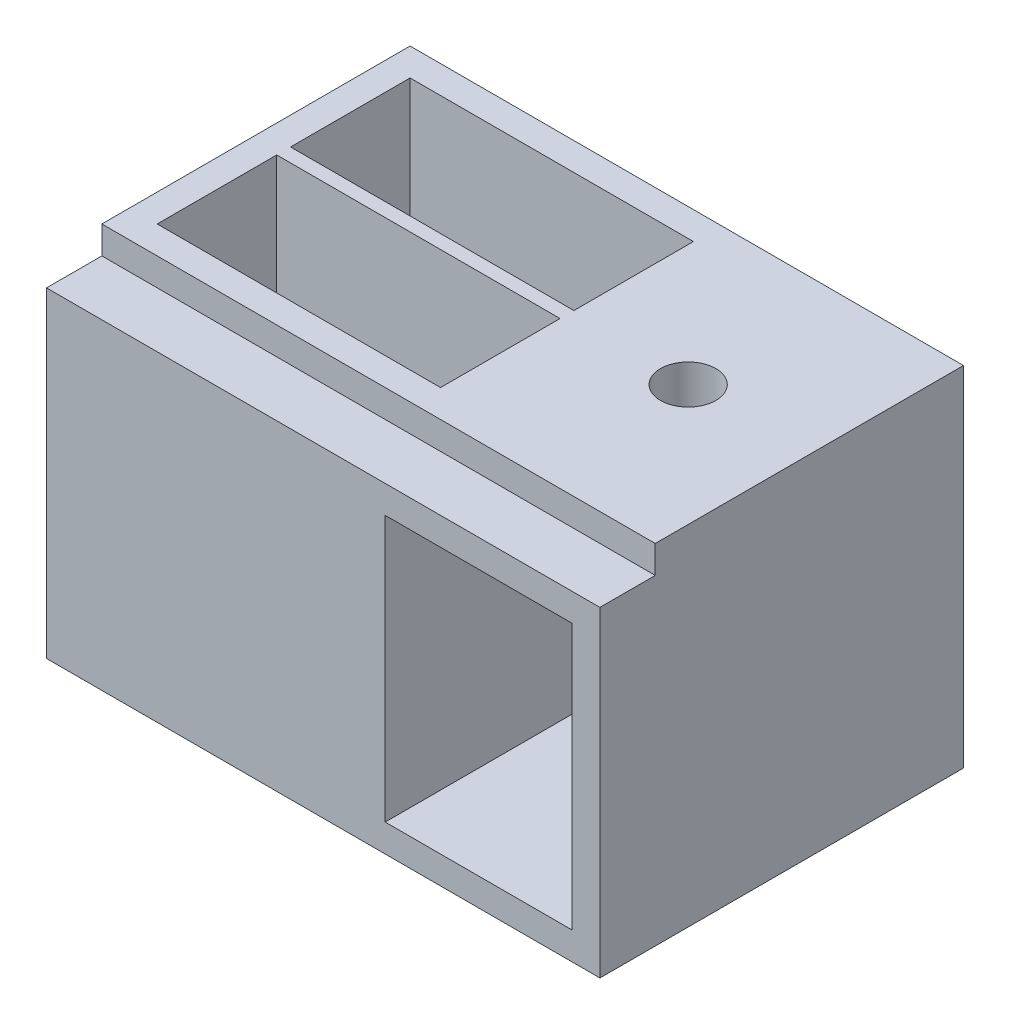
SolidWorks part; units mm, degrees
material "ABS"
ref_plane "Front Plane" through (0, 0, 0) normal (0, 0, 1) x (1, 0, 0)
ref_plane "Top Plane" through (0, 0, 0) normal (0, 1, 0) x (1, 0, 0)
ref_plane "Right Plane" through (0, 0, 0) normal (1, 0, 0) x (0, 0, -1)
sketch "Sketch1" plane through (0, 0, 0) normal (0, 1, 0) x (1, 0, 0)
  line L0 (3.175, 18.4785) -> (3.175, 32.1945)
  line L1 (0, 0) -> (63.5, 0)
  line L2 (0, 0) -> (0, 44.45)
  line L3 (0, 44.45) -> (63.5, 44.45)
  line L4 (63.5, 0) -> (63.5, 44.45)
  line L5 (4.445, 4.445) -> (34.417, 4.445)
  line L6 (4.445, 4.445) -> (4.445, 15.621)
  line L7 (4.445, 15.621) -> (34.417, 15.621)
  line L8 (34.417, 4.445) -> (34.417, 15.621)
  line L9 (4.445, 19.7485) -> (34.417, 19.7485)
  line L10 (4.445, 19.7485) -> (4.445, 30.9245)
  line L11 (4.445, 30.9245) -> (34.417, 30.9245)
  line L12 (34.417, 19.7485) -> (34.417, 30.9245)
  line L13 (3.175, 32.1945) -> (35.687, 32.1945)
  line L14 (35.687, 18.4785) -> (35.687, 32.1945)
  line L15 (3.175, 18.4785) -> (35.687, 18.4785)
  line L16 (3.175, 3.175) -> (35.687, 3.175)
  line L17 (35.687, 3.175) -> (35.687, 16.891)
  line L18 (3.175, 16.891) -> (35.687, 16.891)
  line L19 (3.175, 3.175) -> (3.175, 16.891)
  dimension "D1" = 44.45
  dimension "D2" = 63.5
  dimension "D3" = 11.176
  dimension "D4" = 29.972
  dimension "D5" = 11.176
  dimension "D6" = 29.972
  dimension "D9" = 1.5875
  dimension "D10" = 3.175
  dimension "D11" = 3.175
  dimension "D7" = 1.27
  dimension "D8" = 1.27
extrude "Boss-Extrude1" add sketch "Sketch1" along normal blind 40.005 contours L16 L19 L18 L17 L1 L4 L3 L2 L15 L0 L13 L14 region at (37.4406, 0, -24.3223)
sketch "Sketch2" plane through (0, 0, 0) normal (0, -1, 0) x (1, 0, 0)
  line L0 (3.175, -32.1945) -> (35.687, -32.1945) construction
  line L1 (3.175, -18.4785) -> (3.175, -32.1945) construction
  line L2 (3.175, -18.4785) -> (35.687, -18.4785) construction
  line L3 (35.687, -18.4785) -> (35.687, -32.1945) construction
  line L4 (0, 0) -> (0, -44.45)
  line L5 (0, -44.45) -> (63.5, -44.45)
  line L6 (63.5, -44.45) -> (63.5, 0)
  line L7 (63.5, 0) -> (0, 0)
  line L8 (0, 0) -> (0, -44.45)
  line L9 (0, -44.45) -> (63.5, -44.45)
  line L10 (63.5, -44.45) -> (63.5, 0)
  line L11 (63.5, 0) -> (0, 0)
  line L12 (35.687, -3.175) -> (35.687, -16.891) construction
  line L13 (3.175, -3.175) -> (35.687, -3.175) construction
  line L14 (3.175, -3.175) -> (3.175, -16.891) construction
  line L15 (3.175, -16.891) -> (35.687, -16.891) construction
  line L16 (3.175, -32.1945) -> (35.687, -32.1945)
  line L17 (3.175, -18.4785) -> (3.175, -32.1945)
  line L18 (3.175, -18.4785) -> (35.687, -18.4785)
  line L19 (35.687, -18.4785) -> (35.687, -32.1945)
  line L20 (35.687, -3.175) -> (35.687, -16.891)
  line L21 (3.175, -3.175) -> (35.687, -3.175)
  line L22 (3.175, -3.175) -> (3.175, -16.891)
  line L23 (3.175, -16.891) -> (35.687, -16.891)
  line M9 (3.175, -18.4785) -> (35.687, -18.4785)
  line M10 (35.687, -18.4785) -> (35.687, -32.1945)
  line M11 (35.687, -32.1945) -> (3.175, -32.1945)
  line M12 (3.175, -32.1945) -> (3.175, -18.4785)
  line M13 (3.175, -3.175) -> (35.687, -3.175)
  line M14 (35.687, -3.175) -> (35.687, -16.891)
  line M15 (35.687, -16.891) -> (3.175, -16.891)
  line M16 (3.175, -16.891) -> (3.175, -3.175)
  dimension "D1" = 0
extrude "Boss-Extrude2" add sketch "Sketch2" against normal blind 2.54 contours M13 M16 M15 M14 | M9 M12 M11 M10 region at (19.431, 0, -25.3365) region at (19.431, 0, -10.033)
sketch "Sketch3" plane through (0, 40.005, 0) normal (0, 1, 0) x (1, 0, 0)
  line L33 (35.687, 35.3695) -> (3.175, 35.3695)
  line L34 (35.687, 35.3695) -> (3.175, 35.3695)
  line L36 (0, 32.1945) -> (0, 18.4785)
  line L37 (0, 32.1945) -> (0, 18.4785)
  line L38 (0, 0) -> (63.5, 0) construction
  line L39 (38.862, 18.4785) -> (38.862, 32.1945)
  line L40 (38.862, 18.4785) -> (38.862, 32.1945)
  line L41 (0, 35.3695) -> (38.862, 35.3695)
  line L42 (0, 35.3695) -> (0, 0)
  line L43 (0, 0) -> (38.862, 0)
  line L44 (38.862, 35.3695) -> (38.862, 0)
  line L49 (0, 44.45) -> (0, 0)
  line L50 (0, 0) -> (63.5, 0)
  line L51 (63.5, 0) -> (63.5, 44.45)
  line L52 (63.5, 44.45) -> (0, 44.45)
  line L53 (0, 44.45) -> (0, 0)
  line L54 (0, 0) -> (63.5, 0)
  line L55 (63.5, 0) -> (63.5, 44.45)
  line L56 (63.5, 44.45) -> (0, 44.45)
  line M11 (0, 44.45) -> (0, 0)
  line M12 (0, 0) -> (63.5, 0)
  line M13 (63.5, 0) -> (63.5, 44.45)
  line M14 (63.5, 44.45) -> (0, 44.45)
  dimension "D4" = 0
  dimension "D1" = 3.175
  dimension "D2" = 3.175
  dimension "D3" = 3.175
extrude "Cut-Extrude1" cut sketch "Sketch3" against normal blind 36.83 contours L41 L44 L40 L42 L37 L34 M12 M13 M14 M11 region at (43.4436, 40.005, -26.5347)
sketch "Sketch9" plane through (0, 0, 0) normal (0, 0, 1) x (1, 0, 0)
  line L0 (38.862, 3.175) -> (38.862, 40.005) construction
  line L1 (0, 40.005) -> (38.862, 40.005)
  line L2 (0, 40.005) -> (0, 36.83)
  line L3 (0, 36.83) -> (38.862, 36.83)
  line L4 (38.862, 40.005) -> (38.862, 36.83)
  line L11 (63.5, 3.175) -> (38.862, 3.175)
  line L12 (38.862, 3.175) -> (38.862, 40.005)
  line L13 (38.862, 40.005) -> (0, 40.005)
  line L14 (0, 40.005) -> (0, 0)
  line L15 (0, 0) -> (63.5, 0)
  line L16 (63.5, 0) -> (63.5, 3.175)
  line L18 (38.862, 3.175) -> (38.862, 40.005)
  line L19 (38.862, 40.005) -> (0, 40.005)
  line L20 (0, 40.005) -> (0, 0)
  line L21 (0, 0) -> (63.5, 0)
  line L22 (63.5, 0) -> (63.5, 3.175)
  line L23 (63.5, 3.175) -> (38.862, 3.175)
  line M12 (38.862, 3.175) -> (38.862, 40.005)
  line M14 (0, 40.005) -> (0, 0)
  line M15 (0, 0) -> (63.5, 0)
  line M16 (63.5, 0) -> (63.5, 3.175)
  dimension "D1" = 3.175
  dimension "D2" = 0
extrude "Boss-Extrude8" add sketch "Sketch9" along normal blind 6.35 contours L3 M14 M15 M16 M12 region at (21.0763, 17.543, 0)
sketch "Sketch10" plane through (0, 0, 6.35) normal (0, 0, 1) x (1, 0, 0)
  line L0 (0, 36.83) -> (38.862, 36.83) construction
  line L1 (63.5, 3.175) -> (60.325, 3.175)
  line L2 (63.5, 3.175) -> (63.5, 36.83)
  line L3 (63.5, 36.83) -> (60.325, 36.83)
  line L4 (60.325, 3.175) -> (60.325, 36.83)
  line L5 (38.862, 3.175) -> (38.862, 36.83) construction
  line L7 (60.325, 36.83) -> (60.325, 33.655)
  line L11 (60.325, 33.655) -> (60.325, 30.48)
  line L14 (60.325, 36.83) -> (38.862, 36.83)
  line L15 (60.325, 36.83) -> (60.325, 33.655)
  line L16 (60.325, 33.655) -> (38.862, 33.655)
  line L17 (38.862, 36.83) -> (38.862, 33.655)
  line M8 (63.5, 3.175) -> (38.862, 3.175)
  line M9 (38.862, 3.175) -> (38.862, 36.83)
  dimension "D1" = 3.175
  dimension "D2" = 3.175
  dimension "D3" = 3.175
extrude "Boss-Extrude9" add sketch "Sketch10" against normal up to surface (50.8 mm away) contours L4 L2 L3 M8 | L16 L4 L14 M9 up to face at (31.75, 1.5875, -44.45)
sketch "Sketch11" plane through (0, 0, 0) normal (-1, 0, 0) x (0, 0, 1)
  line L1 (-35.3695, 36.83) -> (-44.45, 36.83)
  line L2 (-35.3695, 36.83) -> (-35.3695, 0)
  line L3 (-35.3695, 0) -> (-44.45, 0)
  line L4 (-44.45, 36.83) -> (-44.45, 0)
extrude "Cut-Extrude2" cut sketch "Sketch11" against normal through all
sketch "Sketch12" plane through (0, 0, -35.3695) normal (0, 0, -1) x (-1, 0, 0)
  line L1 (-60.325, 33.655) -> (-38.862, 33.655)
  line L2 (-60.325, 33.655) -> (-60.325, 3.175)
  line L3 (-60.325, 3.175) -> (-38.862, 3.175)
  line L4 (-38.862, 33.655) -> (-38.862, 3.175)
  circle A0 centre (-49.5935, 18.415) radius 3.175
  line M1 (-38.862, 33.655) -> (-38.862, 3.175)
  line M2 (-38.862, 3.175) -> (-60.325, 3.175)
  line M3 (-60.325, 3.175) -> (-60.325, 33.655)
  line M4 (-60.325, 33.655) -> (-38.862, 33.655)
  dimension "D1" = 6.35
extrude "Boss-Extrude10" add sketch "Sketch12" against normal blind 2.54 contours A0 M1 M4 M3 M2 region at (49.5935, 33.2822, -35.3695)
sketch "Sketch13" plane through (0, 36.83, 0) normal (0, 1, 0) x (1, 0, 0)
  line L0 (63.5, 35.3695) -> (63.5, -6.35) construction
  line L1 (38.862, 35.3695) -> (63.5, 35.3695)
  line L2 (38.862, 35.3695) -> (38.862, 0)
  line L3 (38.862, 0) -> (63.5, 0)
  line L4 (63.5, 35.3695) -> (63.5, 0)
extrude "Boss-Extrude11" add sketch "Sketch13" along normal blind 3.175
sketch "Sketch14" plane through (0, 40.005, 0) normal (0, 1, 0) x (1, 0, 0)
  line L0 (0, 0) -> (63.5, 0) construction
  line L1 (35.687, 0) -> (63.5, 0)
  line L2 (35.687, 0) -> (35.687, 35.3695)
  line L3 (35.687, 35.3695) -> (63.5, 35.3695)
  line L4 (63.5, 0) -> (63.5, 35.3695)
  line L5 (63.5, 0) -> (63.5, 35.3695) construction
  line L6 (0, 35.3695) -> (63.5, 35.3695) construction
  circle A0 centre (49.5935, 17.6847) radius 3.175
  dimension "D1" = 6.35
extrude "Cut-Extrude3" cut sketch "Sketch14" against normal up to surface (6.35 mm away) contours A0 region at (49.5935, 40.005, -17.6847) up to face at (49.5935, 33.655, -13.2397)
